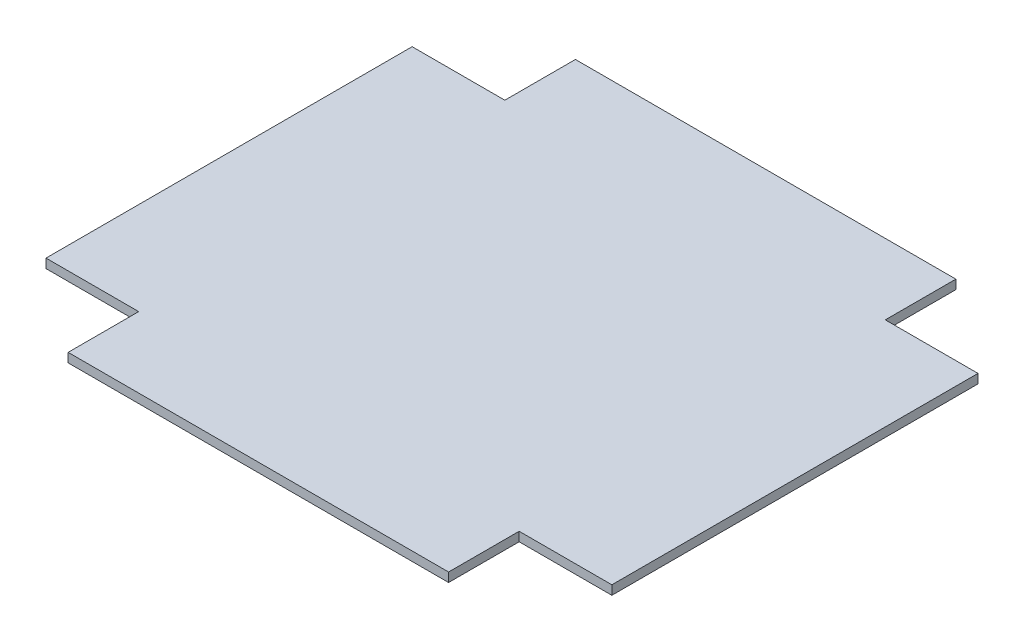
SolidWorks part; units mm, degrees
ref_plane "Front Plane" through (0, 0, 0) normal (0, 0, 1) x (1, 0, 0)
ref_plane "Top Plane" through (0, 0, 0) normal (0, 1, 0) x (1, 0, 0)
ref_plane "Right Plane" through (0, 0, 0) normal (1, 0, 0) x (0, 0, -1)
sketch "Sketch1" plane through (0, 0, 0) normal (0, 1, 0) x (1, 0, 0)
  line L0 (114.3, -110) -> (170, -110)
  line L1 (-170, 110) -> (-114.3, 110)
  line L2 (-170, 110) -> (-170, -110)
  line L3 (-170, -110) -> (-114.3, -110)
  line L4 (170, 110) -> (170, -110)
  line L5 (-170, 110) -> (170, -110) construction
  line L6 (-170, -110) -> (170, 110) construction
  line L7 (114.3, 152.4) -> (-114.3, 152.4)
  line L8 (114.3, 152.4) -> (114.3, 110)
  line L9 (114.3, -152.4) -> (-114.3, -152.4)
  line L10 (-114.3, 152.4) -> (-114.3, 110)
  line L11 (114.3, 152.4) -> (-114.3, -152.4) construction
  line L12 (114.3, -152.4) -> (-114.3, 152.4) construction
  line L13 (114.3, -110) -> (114.3, -152.4)
  line L14 (-114.3, -110) -> (-114.3, -152.4)
  line L15 (114.3, 110) -> (170, 110)
  point P0 (0, 0)
  point P6 (0, 0)
  dimension "D1" = 340
  dimension "D2" = 220
  dimension "D3" = 304.8
  dimension "D4" = 228.6
extrude "Boss-Extrude1" add sketch "Sketch1" along normal blind 5.4864
